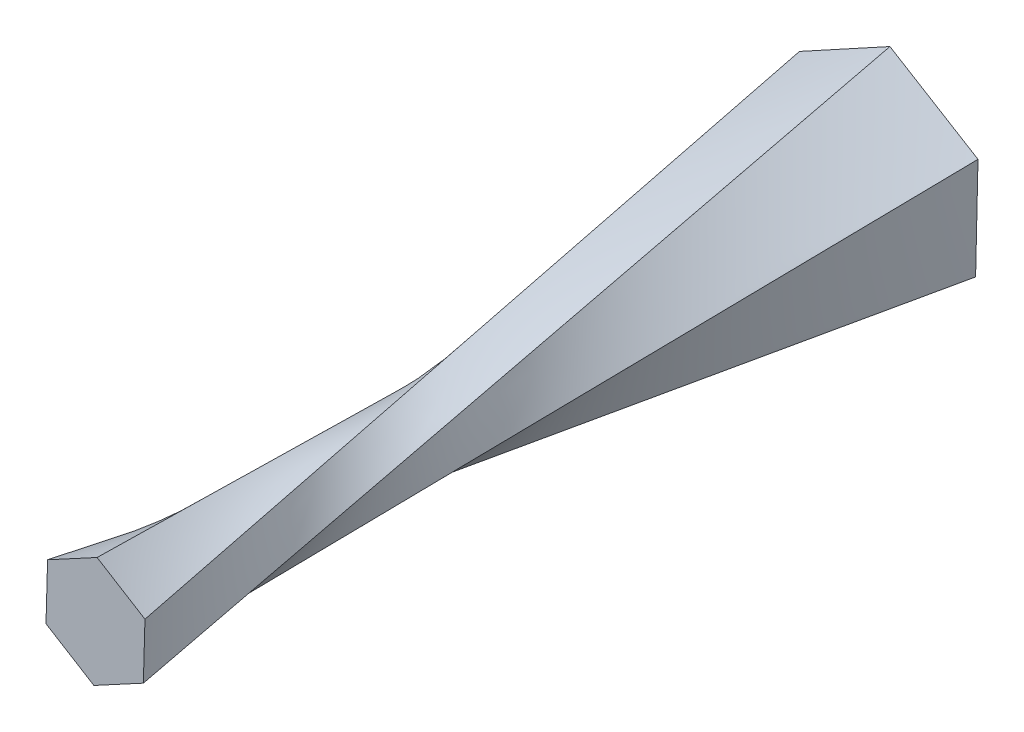
SolidWorks part; units mm, degrees
ref_plane "Front Plane" through (0, 0, 0) normal (0, 0, 1) x (1, 0, 0)
ref_plane "Top Plane" through (0, 0, 0) normal (0, 1, 0) x (1, 0, 0)
ref_plane "Right Plane" through (0, 0, 0) normal (1, 0, 0) x (0, 0, -1)
sketch "Sketch1" plane through (0, 0, 0) normal (0, 0, 1) x (1, 0, 0)
  line L1 (23.2101, 12.6882) -> (0.6168, 26.4446)
  line L2 (0.6168, 26.4446) -> (-22.5933, 13.7564)
  line L3 (-22.5933, 13.7564) -> (-23.2101, -12.6882)
  line L4 (-23.2101, -12.6882) -> (-0.6168, -26.4446)
  line L5 (-0.6168, -26.4446) -> (22.5933, -13.7564)
  line L6 (22.5933, -13.7564) -> (23.2101, 12.6882)
  circle A0 centre (0, 0) radius 22.9079 construction
ref_plane "Plane1" through (0, 0, 203.2) normal (0, 0, 1) x (1, 0, 0)
sketch "Sketch2" plane through (0, 0, 203.2) normal (0, 0, 1) x (1, 0, 0)
  line L1 (12.6941, 6.8566) -> (0.409, 14.4217)
  line L2 (0.409, 14.4217) -> (-12.2851, 7.5651)
  line L3 (-12.2851, 7.5651) -> (-12.6941, -6.8566)
  line L4 (-12.6941, -6.8566) -> (-0.409, -14.4217)
  line L5 (-0.409, -14.4217) -> (12.2851, -7.5651)
  line L6 (12.2851, -7.5651) -> (12.6941, 6.8566)
  circle A0 centre (0, 0) radius 12.4946 construction
ref_plane "Plane2" through (0, 0, 88.9) normal (0, 0, 1) x (1, 0, 0)
sketch "Sketch3" plane through (0, 0, 88.9) normal (0, 0, 1) x (1, 0, 0)
  line L1 (26.222, 15.1958) -> (-0.0489, 30.3069)
  line L2 (-0.0489, 30.3069) -> (-26.271, 15.111)
  line L3 (-26.271, 15.111) -> (-26.222, -15.1958)
  line L4 (-26.222, -15.1958) -> (0.0489, -30.3069)
  line L5 (0.0489, -30.3069) -> (26.271, -15.111)
  line L6 (26.271, -15.111) -> (26.222, 15.1958)
  circle A0 centre (0, 0) radius 26.2465 construction
loft "Loft1" add profiles "Sketch1", "Sketch2" connector at (-0.6168, -26.4446, 0) connector at (-12.2851, 7.5651, 203.2)
